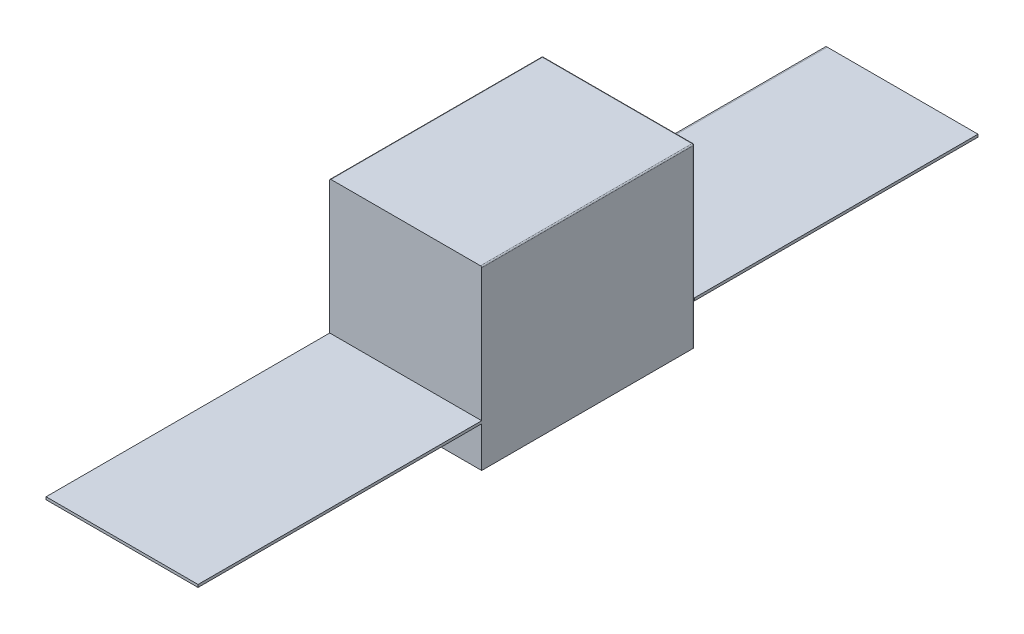
SolidWorks part; units mm, degrees
ref_plane "Alzado" through (0, 0, 0) normal (0, 0, 1) x (1, 0, 0)
ref_plane "Planta" through (0, 0, 0) normal (0, 1, 0) x (1, 0, 0)
ref_plane "Vista lateral" through (0, 0, 0) normal (1, 0, 0) x (0, 0, -1)
sketch "Croquis1" plane through (0, 0, 0) normal (0, 0, 1) x (1, 0, 0)
  line L1 (0, 0) -> (15000, 0)
  line L2 (0, 0) -> (0, 7000)
  line L3 (0, 7000) -> (15000, 7000)
  line L4 (15000, 0) -> (15000, 7000)
  dimension "D1" = 15000
  dimension "D2" = 7000
extrude "Saliente-Extruir1" add sketch "Croquis1" along normal blind 12000
sketch "Croquis2" plane through (0, 7000, 0) normal (0, 1, 0) x (1, 0, 0)
  line L0 (15000, 0) -> (0, 0) construction
  line L1 (250, -250) -> (14750, -250)
  line L2 (250, -250) -> (250, -11800)
  line L3 (250, -11800) -> (14750, -11800)
  line L4 (14750, -250) -> (14750, -11800)
  line L5 (0, -12000) -> (0, 0) construction
  line L6 (15000, -12000) -> (15000, 0) construction
  line L7 (15000, -12000) -> (0, -12000) construction
  dimension "D1" = 250
  dimension "D2" = 250
  dimension "D3" = 250
  dimension "D4" = 200
extrude "Cortar-Extruir1" cut sketch "Croquis2" against normal blind 6750
sketch "Croquis3" plane through (0, 0, 0) normal (-1, 0, 0) x (0, 0, 1)
  line L0 (12000, 0) -> (0, 0) construction
  line L1 (5500, 250) -> (8500, 250)
  line L2 (5500, 250) -> (5500, 4750)
  line L3 (5500, 4750) -> (8500, 4750)
  line L4 (8500, 250) -> (8500, 4750)
  line L5 (12000, 7000) -> (12000, 0) construction
  dimension "D1" = 250
  dimension "D2" = 3000
  dimension "D3" = 3500
  dimension "D4" = 4500
extrude "Cortar-Extruir2" cut sketch "Croquis3" against normal blind 250
sketch "Croquis8" plane through (0, 7000, 0) normal (0, 1, 0) x (1, 0, 0)
  line L1 (15000, -12000) -> (0, -12000)
  line L2 (15000, -12000) -> (15000, 0)
  line L3 (15000, 0) -> (0, 0)
  line L4 (0, -12000) -> (0, 0)
extrude "Saliente-Extruir3" add sketch "Croquis8" along normal blind 250
sketch "Croquis9" plane through (0, 7250, 0) normal (0, 1, 0) x (1, 0, 0)
  line L1 (14750, -250) -> (250, -250)
  line L2 (14750, -250) -> (14750, -11800)
  line L3 (14750, -11800) -> (250, -11800)
  line L4 (250, -250) -> (250, -11800)
  line L5 (14750, -250) -> (250, -250)
  line L6 (14750, -250) -> (14750, -11800)
  line L7 (14750, -11800) -> (250, -11800)
  line L8 (250, -250) -> (250, -11800)
  line L9 (0, -12000) -> (15000, -12000)
  line L10 (0, -12000) -> (0, 0)
  line L11 (0, 0) -> (15000, 0)
  line L12 (15000, -12000) -> (15000, 0)
  line M1 (15000, -12000) -> (15000, 0)
  line M2 (15000, 0) -> (0, 0)
  line M3 (0, 0) -> (0, -12000)
  line M4 (0, -12000) -> (15000, -12000)
extrude "Saliente-Extruir4" add sketch "Croquis9" along normal blind 6000 contours L4 L1 L2 L3 M4 M1 M2 M3 region at (192.0937, 7250, 6000)
sketch "Croquis10" plane through (0, 0, 0) normal (0, 0, -1) x (-1, 0, 0)
  line L0 (-14750, 250) -> (-250, 250) construction
  line L1 (-350, 250) -> (-2150, 250)
  line L2 (-350, 250) -> (-350, 4750)
  line L3 (-350, 4750) -> (-2150, 4750)
  line L4 (-2150, 250) -> (-2150, 4750)
  line L5 (-250, 250) -> (-250, 7000) construction
  dimension "D1" = 100
  dimension "D2" = 1800
extrude "Cortar-Extruir3" cut sketch "Croquis10" against normal up to surface (250 mm away) up to face at (7500, 3625, 250)
sketch "Croquis11" plane through (0, 0, 0) normal (0, 0, -1) x (-1, 0, 0)
  line L0 (-250, 13250) -> (0, 13250)
  line L1 (-15000, 13250) -> (-14750, 13250)
  line L2 (-15000, 13250) -> (-15000, 0)
  line L3 (-15000, 0) -> (0, 0)
  line L4 (0, 13250) -> (0, 0)
  line L5 (-14750, 250) -> (-250, 250)
  line L6 (-14750, 250) -> (-14750, 13250)
  line L8 (-250, 250) -> (-250, 13250)
extrude "Saliente-Extruir5" add sketch "Croquis11" along normal blind 9000
sketch "Croquis12" plane through (0, 0, -9000) normal (0, 0, -1) x (-1, 0, 0)
  line L1 (-14750, 13250) -> (-250, 13250)
  line L2 (-14750, 13250) -> (-14750, 250)
  line L3 (-14750, 250) -> (-250, 250)
  line L4 (-250, 13250) -> (-250, 250)
extrude "Saliente-Extruir6" add sketch "Croquis12" against normal blind 200
sketch "Croquis13" plane through (0, 13250, 0) normal (0, 1, 0) x (1, 0, 0)
  line L1 (15000, 9000) -> (0, 9000)
  line L2 (15000, 9000) -> (15000, -12000)
  line L3 (15000, -12000) -> (0, -12000)
  line L4 (0, 9000) -> (0, -12000)
extrude "Saliente-Extruir7" add sketch "Croquis13" along normal blind 200
sketch "Croquis17" plane through (0, 0, -9000) normal (0, 0, -1) x (-1, 0, 0)
  line L0 (0, 0) -> (0, 13450) construction
  line L1 (-6250, 4750) -> (-250, 4750)
  line L2 (-6250, 4750) -> (-6250, 250)
  line L3 (-6250, 250) -> (-250, 250)
  line L4 (-250, 4750) -> (-250, 250)
  line L5 (-15000, 0) -> (0, 0) construction
  dimension "D1" = 250
  dimension "D2" = 250
  dimension "D3" = 6000
  dimension "D4" = 4500
extrude "Cortar-Extruir5" cut sketch "Croquis17" against normal blind 250
fillet "Redondeo1" radius 120 5 edges at (15000, 13450, 1500) (15000, 6725, -9000) (0, 13450, 1500) (7500, 13450, -9000) (0, 6725, -9000)
sketch "Croquis18" plane through (0, 0, 0) normal (-1, 0, 0) x (0, 0, 1)
  line L0 (-5061.5932, 10023.2477) -> (8131.3974, 10023.2477) construction
  line L1 (-5061.5932, 8935.6512) -> (8131.3974, 8935.6512) construction
  text T0 "      SUBESTACION ENCAPSULADA" font "Century Gothic" height in points 2000
  text T1 "                  115 KV/ 13.8 KV" font "Century Gothic" height in points 2000
extrude "Saliente-Extruir8" add sketch "Croquis18" along normal blind 20
sketch "Croquis19" plane through (0, 0, 0) normal (-1, 0, 0) x (0, 0, 1)
  line L1 (-4467.8681, 11031.5872) -> (7304.6642, 11031.5872)
  line L2 (-4467.8681, 11031.5872) -> (-4467.8681, 8540.3809)
  line L3 (-4467.8681, 8540.3809) -> (7304.6642, 8540.3809)
  line L4 (7304.6642, 11031.5872) -> (7304.6642, 8540.3809)
extrude "Saliente-Extruir9" add sketch "Croquis19" along normal blind 10
sketch "Croquis20" plane through (0, 0, 0) normal (0, -1, 0) x (1, 0, 0)
  line L0 (120, -9000) -> (14880, -9000)
  line L1 (15000, -8880) -> (15000, 12000)
  line L2 (15000, 12000) -> (0, 12000)
  line L3 (0, 12000) -> (0, -8880)
  line L5 (14750, 11750) -> (250, 11750)
  line L6 (14750, 11750) -> (14750, -8750)
  line L7 (14750, -8750) -> (250, -8750)
  line L8 (250, 11750) -> (250, -8750)
  arc A0 (0, -8880) -> (120, -9000) centre (120, -8880) ccw
  arc A1 (14880, -9000) -> (15000, -8880) centre (14880, -8880) ccw
  dimension "D1" = 250
  dimension "D2" = 250
  dimension "D3" = 250
  dimension "D4" = 250
extrude "Saliente-Extruir10" add sketch "Croquis20" along normal blind 4000
sketch "Croquis21" plane through (0, 0, 0) normal (-1, 0, 0) x (0, 0, 1)
  line L0 (12000, 13330) -> (12000, -4000) construction
  line L1 (-37000, 250) -> (40000, 250)
  line L2 (-37000, 250) -> (-37000, 0)
  line L3 (-37000, 0) -> (40000, 0)
  line L4 (40000, 250) -> (40000, 0)
  line L5 (-9000, -4000) -> (-9000, 13330) construction
  dimension "D1" = 28000
  dimension "D2" = 28000
extrude "Saliente-Extruir11" add sketch "Croquis21" along normal blind 10
sketch "Croquis22" plane through (0, 0, 0) normal (1, 0, 0) x (0, 0, -1)
  line L1 (-12000, 250) -> (-40000, 250)
  line L2 (-12000, 250) -> (-12000, 0)
  line L3 (-12000, 0) -> (-40000, 0)
  line L4 (-40000, 250) -> (-40000, 0)
  line L5 (9000, 250) -> (37000, 250)
  line L6 (9000, 250) -> (9000, 0)
  line L7 (9000, 0) -> (37000, 0)
  line L8 (37000, 250) -> (37000, 0)
extrude "Saliente-Extruir12" add sketch "Croquis22" along normal up to surface (15000 mm away) up to face at (15000, 4665, 1560)
sketch "Croquis23" plane through (0, 250, 0) normal (0, 1, 0) x (1, 0, 0)
  line L1 (15000, 37000) -> (120, 37000)
  line L2 (15000, 37000) -> (15000, 8880)
  line L3 (15000, 8880) -> (120, 8880)
  line L4 (120, 37000) -> (120, 8880)
  line L5 (15000, -40000) -> (0, -40000)
  line L6 (15000, -40000) -> (15000, -12000)
  line L7 (15000, -12000) -> (0, -12000)
  line L8 (0, -40000) -> (0, -12000)
extrude "Saliente-Extruir13" add sketch "Croquis23" along normal blind 10
sketch "Croquis24" plane through (0, 0, 0) normal (-1, 0, 0) x (0, 0, 1)
  line L0 (8500, 4750) -> (-2500, 4750)
  line L1 (-2500, 4750) -> (-2500, 250)
  line L2 (40000, 250) -> (-37000, 250) construction
  line L3 (-2500, 250) -> (8500, 250)
  line L4 (8500, 250) -> (8500, 4750)
  dimension "D1" = 11000
extrude "Cortar-Extruir6" cut sketch "Croquis24" against normal blind 250
